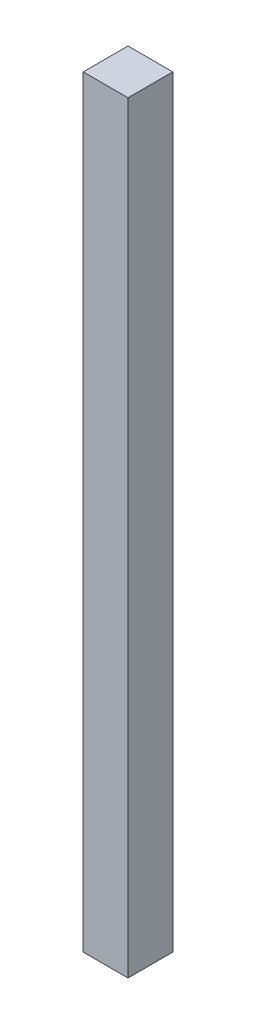
SolidWorks part; units mm, degrees
material "Concreto"
ref_plane "Plano frontal" through (0, 0, 0) normal (0, 0, 1) x (1, 0, 0)
ref_plane "Plano superior" through (0, 0, 0) normal (0, 1, 0) x (1, 0, 0)
ref_plane "Plano direito" through (0, 0, 0) normal (1, 0, 0) x (0, 0, -1)
sketch "Esboço1" plane through (0, 0, 0) normal (0, 1, 0) x (1, 0, 0)
  line L0 (50, 0) -> (-50, 0) construction
  line L1 (-50, 50) -> (50, 50)
  line L2 (-50, 50) -> (-50, -50)
  line L3 (-50, -50) -> (50, -50)
  line L4 (50, 50) -> (50, -50)
  line L5 (-50, 50) -> (50, -50) construction
  line L6 (-50, -50) -> (50, 50) construction
  point P0 (0, 0)
  dimension "D1" = 100
  dimension "D2" = 100
extrude "Ressalto-extrusão1" add sketch "Esboço1" along normal blind 1700
